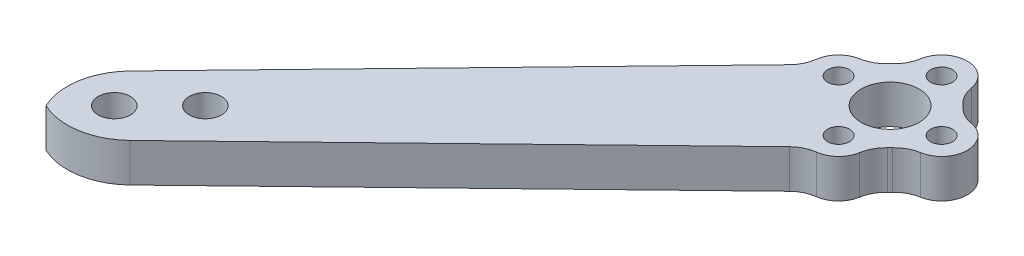
SolidWorks part; units mm, degrees
ref_plane "Front Plane" through (0, 0, 0) normal (0, 0, 1) x (1, 0, 0)
ref_plane "Top Plane" through (0, 0, 0) normal (0, 1, 0) x (1, 0, 0)
ref_plane "Right Plane" through (0, 0, 0) normal (1, 0, 0) x (0, 0, -1)
sketch "Sketch1" plane through (0, 0, 0) normal (0, 1, 0) x (1, 0, 0)
  line L1 (85, -85) -> (-85, -85) construction
  line L2 (85, -85) -> (85, 85) construction
  line L3 (85, 85) -> (-85, 85) construction
  line L4 (-85, -85) -> (-85, 85) construction
  line L5 (85, -85) -> (-85, 85) construction
  line L6 (85, 85) -> (-85, -85) construction
  point P0 (0, 0)
  dimension "D1" = 170
  dimension "D2" = 170
sketch "Sketch7" plane through (0, 0, 0) normal (0, 1, 0) x (1, 0, 0)
  line L0 (85, -85) -> (-85, 85) construction
  line L1 (25, -25) -> (-25, -25) construction
  line L2 (25, -25) -> (25, 25) construction
  line L3 (25, 25) -> (-25, 25) construction
  line L4 (-25, -25) -> (-25, 25) construction
  line L5 (25, -25) -> (-25, 25) construction
  line L6 (25, 25) -> (-25, -25) construction
  circle A0 centre (24.7487, 24.7487) radius 2.5
  circle A1 centre (31.8198, 31.8198) radius 2.5
  point P0 (0, 0)
  dimension "D2" = 5
  dimension "D3" = 5
  dimension "D1" = 50
  dimension "D4" = 35
  dimension "D5" = 45
sketch "Sketch2" plane through (0, 0, 0) normal (0, 1, 0) x (1, 0, 0)
  line L7 (82.7012, 71.6708) -> (23.5806, 14.468)
  line L10 (14.468, 23.5806) -> (71.6708, 82.7012)
  line L23 (14.468, 23.5806) -> (23.5806, 14.468)
  arc A0 (79.539, 90.8462) -> (79.1538, 90.461) centre (85, 85) ccw
  circle A4 centre (85, 93) radius 1.7
  circle A5 centre (93, 85) radius 1.7
  circle A6 centre (85, 77) radius 1.7
  circle A7 centre (77, 85) radius 1.7
  arc A8 (76.3333, 88.9441) -> (73.0344, 85.5236) centre (77, 85) ccw
  arc A9 (88.9441, 93.6667) -> (81.0559, 93.6667) centre (85, 93) ccw
  arc A10 (93.6667, 81.0559) -> (93.6667, 88.9441) centre (93, 85) ccw
  arc A11 (85.5236, 73.0344) -> (88.9441, 76.3333) centre (85, 77) ccw
  arc A12 (90.8462, 90.461) -> (90.461, 90.8462) centre (85, 85) ccw
  arc A13 (90.461, 79.1538) -> (90.8462, 79.539) centre (85, 85) ccw
  arc A15 (93.6667, 81.0559) -> (90.8462, 79.539) centre (94.5, 76.1259) ccw
  arc A16 (90.461, 79.1538) -> (88.9441, 76.3333) centre (93.8741, 75.5) ccw
  arc A17 (79.539, 90.8462) -> (81.0559, 93.6667) centre (76.1259, 94.5) ccw
  arc A18 (76.3333, 88.9441) -> (79.1538, 90.461) centre (75.5, 93.8741) ccw
  arc A19 (93.6667, 88.9441) -> (90.8462, 90.461) centre (94.5, 93.8741) cw
  arc A20 (88.9441, 93.6667) -> (90.461, 90.8462) centre (93.8741, 94.5) ccw
  arc A23 (85.5236, 73.0344) -> (82.7012, 71.6708) centre (86.178, 68.0774) ccw
  arc A24 (73.0344, 85.5236) -> (71.6708, 82.7012) centre (68.0774, 86.178) cw
  circle A82 centre (85, 85) radius 4.5
  point P28 (92, 88.873)
  point P146 (0, 0)
  dimension "D1" = 5
  dimension "D2" = 5
  dimension "D5" = 5
extrude "Boss-Extrude1" add sketch "Sketch2" along normal blind 6
sketch "Sketch6" plane through (0, 0, 0) normal (0, 1, 0) x (1, 0, 0)
  circle A0 centre (85, 85) radius 14 construction
  circle A1 centre (85, 85) radius 63.5 construction
  circle A2 centre (85, -85) radius 63.5 construction
  circle A3 centre (-85, -85) radius 63.5 construction
  circle A4 centre (-85, 85) radius 63.5 construction
fillet "Fillet1" radius 10 2 edges at (23.5806, 3, -14.468) (14.468, 3, -23.5806)
extrude "Cut-Extrude2" cut sketch "Sketch7" against normal through all both and the other way through all
